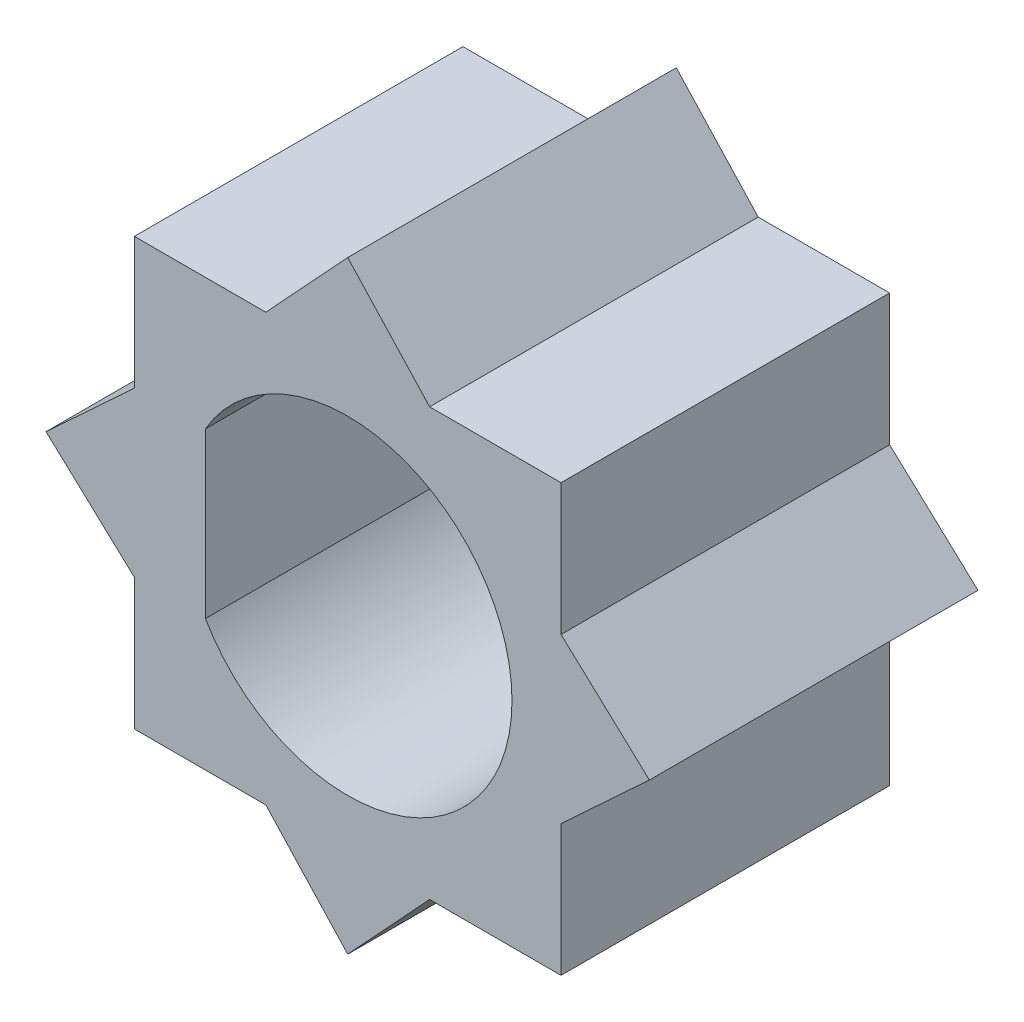
SolidWorks part; units mm, degrees
ref_plane "Plan de face" through (0, 0, 0) normal (0, 0, 1) x (1, 0, 0)
ref_plane "Plan de dessus" through (0, 0, 0) normal (0, 1, 0) x (1, 0, 0)
ref_plane "Plan de droite" through (0, 0, 0) normal (1, 0, 0) x (0, 0, -1)
sketch "Esquisse1" plane through (0, 0, 0) normal (0, 0, 1) x (1, 0, 0)
  line L0 (-16.0398, 7.7529) -> (-16.0398, 4.7529)
  line L1 (-17.3372, 10.1483) -> (-9.5463, 10.1483)
  line L2 (-17.3372, 10.1483) -> (-17.3372, 2.3574)
  line L3 (-9.5463, 10.1483) -> (-9.5463, 2.3574)
  line L4 (-17.3372, 2.3574) -> (-9.5463, 2.3574)
  line L5 (-13.4418, 11.7619) -> (-14.9372, 10.1483)
  line L6 (-13.4418, 11.7619) -> (-11.9463, 10.1483)
  line L7 (-18.9508, 6.2529) -> (-17.3372, 7.7483)
  line L8 (-18.9508, 6.2529) -> (-17.3372, 4.7574)
  line L9 (-13.4418, 0.7438) -> (-14.9372, 2.3574)
  line L10 (-13.4418, 0.7438) -> (-11.9463, 2.3574)
  line L11 (-9.5463, 7.7483) -> (-7.9327, 6.2529)
  line L12 (-9.5463, 4.7574) -> (-7.9327, 6.2529)
  circle A0 centre (-13.4418, 6.2529) radius 3
  circle A1 centre (-13.4418, 6.2529) radius 5.509
  dimension "D1" = 6
  dimension "D2" = 3
  dimension "D3" = 2.2
  dimension "D4" = 2.4
  dimension "D5" = 2.4
  dimension "D6" = 2.2
  dimension "D7" = 2.2
  dimension "D8" = 2.4
  dimension "D9" = 2.4
  dimension "D10" = 2.4
  dimension "D11" = 2.2
  dimension "D12" = 2.2
  dimension "D13" = 2.2
  dimension "D14" = 0
extrude "Boss.-Extru.1" add sketch "Esquisse1" along normal blind 6 contours L7 L8 L2 | L2 L4 L3 L1 A0 | L0 A0 | L6 L5 L1 | L3 L12 L11 | L9 L10 L4 region at (-16.2016, 6.2529, 0) region at (-16.1372, 10.0382, 0) region at (-13.4418, 10.6862, 0) region at (-17.8751, 6.2529, 0) region at (-9.0084, 6.2529, 0) region at (-13.4418, 1.8195, 0)
